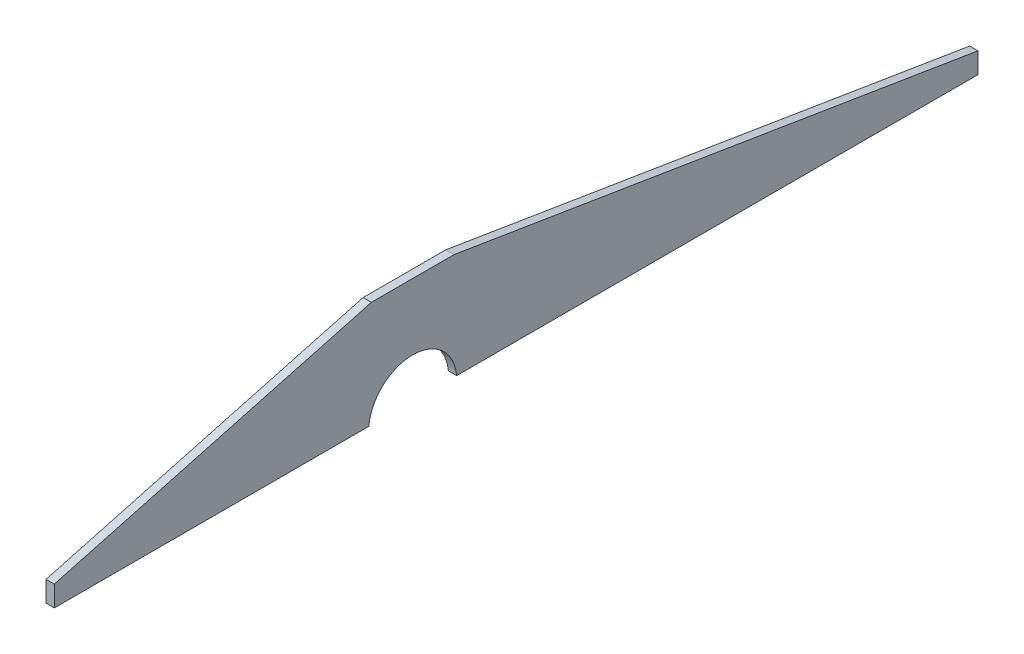
SolidWorks part; units mm, degrees
material "AISI 304"
ref_plane "Front Plane" through (0, 0, 0) normal (0, 0, 1) x (1, 0, 0)
ref_plane "Top Plane" through (0, 0, 0) normal (0, 1, 0) x (1, 0, 0)
ref_plane "Right Plane" through (0, 0, 0) normal (1, 0, 0) x (0, 0, -1)
sketch "Sketch1" plane through (0, 0, 0) normal (1, 0, 0) x (0, 0, -1)
  line L0 (-31.8591, 3) -> (-260, 3)
  line L1 (-260, 3) -> (-260, 18)
  line L2 (-260, 18) -> (-30, 80)
  line L3 (-30, 80) -> (30, 80)
  line L4 (30, 80) -> (410, 18)
  line L5 (410, 18) -> (410, 3)
  line L6 (410, 3) -> (31.8591, 3)
  arc A0 (31.8591, 3) -> (-31.8591, 3) centre (0, 0) ccw
  point P12 (0, 80)
  dimension "D1" = 64
  dimension "D2" = 15
  dimension "D3" = 15
  dimension "D4" = 60
  dimension "D5" = 80
  dimension "D6" = 260
  dimension "D7" = 410
  dimension "D8" = 3
base flange "Base-Flange1" sketch "Sketch1" thickness 6 reverse thickness direction no parameters "D1"=0
sketch "Bend-Lines1" [suppressed] plane through (0, 0, 0) normal (0, 1, 0) x (1, 0, 0)
sketch "Bounding-Box1" [suppressed] plane through (0, 0, 0) normal (0, 1, 0) x (1, 0, 0)
sheet metal parameters "Sheet-Metal3" thickness 6 parameters "D1"=0
flat pattern "Flat-Pattern3" [suppressed]
sketch "Bend-Lines2" plane through (0, 0, 0) normal (0, 1, 0) x (1, 0, 0)
sketch3d "Bounding-Box2" [suppressed]
  line L0 (-260, 3, 0) -> (410, 3, 0) construction
  line L1 (-260, 80, 0) -> (410, 80, 0) construction
  line L2 (-260, 3, 0) -> (-260, 80, 0) construction
  line L3 (410, 3, 0) -> (410, 80, 0) construction
